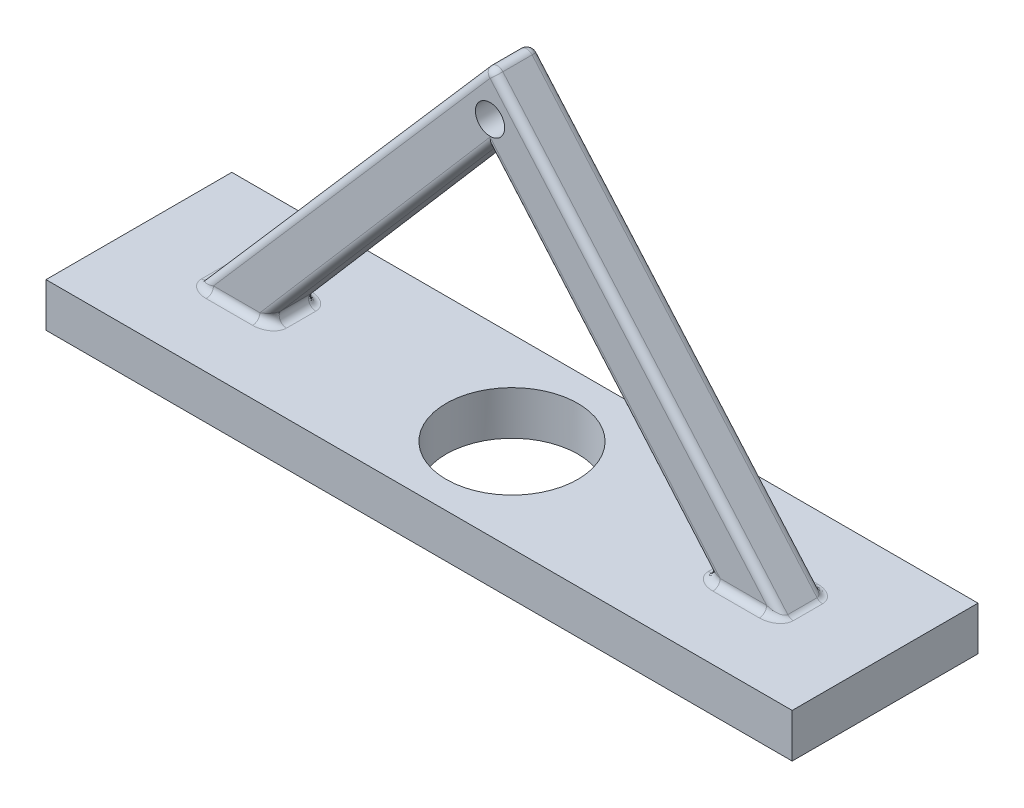
SolidWorks part; units mm, degrees
other "Markup1"
sketch "Sketch14" plane through (-25.5, 17.6996, 6.35) normal (-0.0114, 0.3815, 0.9243) x (0.9999, 0.0065, 0.0096)
ref_plane "Front Plane" through (0, 0, 0) normal (0, 0, 1) x (1, 0, 0)
ref_plane "Top Plane" through (0, 0, 0) normal (0, 1, 0) x (1, 0, 0)
ref_plane "Right Plane" through (0, 0, 0) normal (1, 0, 0) x (0, 0, -1)
sketch "Sketch1" plane through (0, 0, 0) normal (0, 1, 0) x (1, 0, 0)
  line L1 (-25.5, -6.35) -> (25.5, -6.35)
  line L2 (-25.5, -6.35) -> (-25.5, 6.35)
  line L3 (-25.5, 6.35) -> (25.5, 6.35)
  line L4 (25.5, -6.35) -> (25.5, 6.35)
  point P4 (-25.5, 0)
  point P6 (0, 6.35)
  point P7 (0, -6.35)
  dimension "D1" = 51
  dimension "D2" = 12.7
extrude "Boss-Extrude1" add sketch "Sketch1" along normal blind 3
sketch "Sketch7" plane through (0, 0, 0) normal (0, 0, 1) x (1, 0, 0)
  line L0 (-20, 3) -> (0, 26)
  line L1 (-25.5, 3) -> (25.5, 3) construction
  line L2 (0, 26) -> (20, 3)
  line L3 (-25.5, 3) -> (25.5, 3) construction
  line L4 (0, 26) -> (0, 3) construction
  line L5 (-20, 3) -> (20, 3)
  dimension "D1" = 23
  dimension "D2" = 40
extrude "Boss-Extrude2" add sketch "Sketch7" along normal mid plane 3
sketch "Sketch9" plane through (0, 0, 1.5) normal (0, 0, 1) x (1, 0, 0)
  line L0 (0, 21) -> (-15.5, 3)
  line L1 (-15.5, 3) -> (15.5, 3)
  line L2 (15.5, 3) -> (0, 21)
  line L3 (0, 21) -> (0, 3) construction
  line L4 (-20, 3) -> (20, 3) construction
  dimension "D1" = 31
  dimension "D2" = 18
extrude "Cut-Extrude1" cut sketch "Sketch9" against normal through all both and the other way through all
sketch "Sketch13" plane through (0, 0, 1.5) normal (0, 0, 1) x (1, 0, 0)
  circle A0 centre (0, 22.8096) radius 1
  point P2 (0, 20.477)
  point P3 (0, 19.9867)
  point P4 (0, 22.8096)
  dimension "D1" = 2
extrude "Cut-Extrude2" cut sketch "Sketch13" against normal blind 3
fillet "Fillet1" radius 0.5 17 edges at (7.75, 12, 1.5) (-7.75, 12, 1.5) (-7.75, 12, -1.5) (7.75, 12, -1.5) (10, 14.5, -1.5) (-10, 14.5, -1.5) (-10, 14.5, 1.5) (10, 14.5, 1.5) (0, 26, 0) (-20, 3, 0) (-17.75, 3, 1.5) (-17.75, 3, -1.5) (-15.5, 3, 0) (17.75, 3, -1.5) (20, 3, 0) (17.75, 3, 1.5) (15.5, 3, 0)
sketch "Sketch15" plane through (0, 3, 0) normal (0, 1, 0) x (1, 0, 0)
  line L0 (0, 6.35) -> (0, -6.35) construction
  circle A0 centre (0, 0) radius 4.5
  dimension "D1" = 9
extrude "Cut-Extrude3" cut sketch "Sketch15" against normal blind 10
